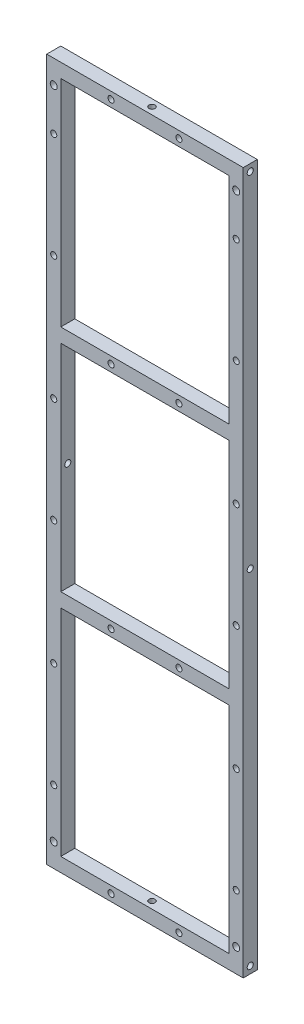
SolidWorks part; units mm, degrees
material "Alumina"
ref_plane "Front Plane" through (0, 0, 0) normal (0, 0, 1) x (1, 0, 0)
ref_plane "Top Plane" through (0, 0, 0) normal (0, 1, 0) x (1, 0, 0)
ref_plane "Right Plane" through (0, 0, 0) normal (1, 0, 0) x (0, 0, -1)
sketch "Sketch1" plane through (0, 0, 0) normal (0, 0, 1) x (1, 0, 0)
  line L0 (36, 144) -> (36, 52)
  line L9 (-42, -150) -> (42, -150)
  line L10 (-42, -150) -> (-42, 150)
  line L11 (-42, 150) -> (42, 150)
  line L12 (42, -150) -> (42, 150)
  line L13 (0, 0) -> (0, 46) construction
  line L15 (-36, -144) -> (36, -144)
  line L16 (-36, -144) -> (-36, -52)
  line L17 (-36, 144) -> (36, 144)
  line L21 (-36, 52) -> (36, 52)
  line L23 (-36, 46) -> (36, 46)
  line L25 (-36, -46) -> (36, -46)
  line L27 (-36, -52) -> (36, -52)
  line L33 (36, 46) -> (36, -46)
  line L34 (-36, 52) -> (-36, 144)
  line L35 (-36, -46) -> (-36, 46)
  line L36 (36, -52) -> (36, -144)
  dimension "D1" = 84
  dimension "D2" = 300
  dimension "D3" = 72
  dimension "D4" = 288
  dimension "D5" = 6
  dimension "D6" = 92
  dimension "D7" = 6
  dimension "D8" = 92
  dimension "D9" = 6
  dimension "D10" = 6
  dimension "D11" = 92
  dimension "D12" = 46
  dimension "D13" = 6
extrude "Boss-Extrude1" add sketch "Sketch1" along normal blind 6
sketch "Sketch2" plane through (42, 0, 0) normal (1, 0, 0) x (0, 0, -1)
  line L0 (-6, 150) -> (0, 150) construction
  line L1 (-6, -150) -> (-6, 150) construction
  line L3 (-3, 147) -> (-3, 0) construction
  circle A0 centre (-3, 147) radius 1.3
  circle A4 centre (-3, 0) radius 1.3
  circle A5 centre (-3, -147) radius 1.3
  circle A6 centre (-3, -294) radius 1.3
  dimension "D1" = 3
  dimension "D3" = 2.6
  dimension "D4" = 3
  dimension "D2" = 4
  dimension "D5" = 147
extrude "Cut-Extrude1" cut sketch "Sketch2" against normal blind 10
mirror "Mirror1" about plane through (0, 0, 0) normal (1, 0, 0) of "Cut-Extrude1"
sketch "Sketch4" plane through (0, 0, 6) normal (0, 0, 1) x (1, 0, 0)
  line L0 (-42, -150) -> (-42, 150) construction
  line L1 (42, -150) -> (42, 150) construction
  line L2 (-42, 150) -> (42, 150) construction
  line L3 (42, 150) -> (-42, 150) construction
  line L4 (-14.5, 147) -> (-14.5, 49) construction
  line L6 (-39, 122) -> (39, 122) construction
  line L7 (-39, 122) -> (-39, 77) construction
  line L8 (-39, 122) -> (-39, 24) construction
  circle A0 centre (-14.5, 147) radius 1.3
  circle A1 centre (14.5, 147) radius 1.3
  circle A8 centre (-39, 122) radius 1.3
  circle A20 centre (-14.5, 49) radius 1.3
  circle A21 centre (14.5, 49) radius 1.3
  circle A22 centre (-14.5, -49) radius 1.3
  circle A23 centre (14.5, -49) radius 1.3
  circle A24 centre (-14.5, -147) radius 1.3
  circle A25 centre (14.5, -147) radius 1.3
  circle A29 centre (39, 122) radius 1.3
  circle A30 centre (39, 77) radius 1.3
  circle A31 centre (-39, 77) radius 1.3
  circle A32 centre (-39, 24) radius 1.3
  circle A33 centre (39, 24) radius 1.3
  circle A34 centre (39, -21) radius 1.3
  circle A35 centre (-39, -21) radius 1.3
  circle A36 centre (-39, -74) radius 1.3
  circle A37 centre (39, -74) radius 1.3
  circle A38 centre (39, -119) radius 1.3
  circle A39 centre (-39, -119) radius 1.3
  dimension "D1" = 27.5
  dimension "D4" = 78
  dimension "D7" = 45
  dimension "D10" = 2.6
  dimension "D11" = 2.6
  dimension "D3" = 3
  dimension "D6" = 3
  dimension "D14" = 2.6
  dimension "D15" = 2
  dimension "D16" = 98
  dimension "D2" = 27.5
  dimension "D5" = 28
  dimension "D9" = 3
  dimension "D13" = 98
  dimension "D12" = 4
  dimension "D8" = 2
extrude "Cut-Extrude3" cut sketch "Sketch4" against normal blind 10
sketch "Sketch5" plane through (0, 150, 0) normal (0, 1, 0) x (1, 0, 0)
  line L0 (42, -6) -> (-42, -6) construction
  circle A0 centre (0, -3) radius 1.3
  point P5 (0, -6)
  dimension "D1" = 3
  dimension "D2" = 2.6
extrude "Cut-Extrude4" cut sketch "Sketch5" against normal blind 10
mirror "Mirror2" about plane through (0, 0, 0) normal (0, 1, 0) of "Cut-Extrude4"
sketch "Sketch6" plane through (0, 0, 6) normal (0, 0, 1) x (1, 0, 0)
  line L0 (-42, 150) -> (-42, -150) construction
  line L1 (42, 150) -> (-42, 150) construction
  circle A0 centre (-39, 140) radius 1.5
  dimension "D1" = 3
  dimension "D2" = 3
  dimension "D3" = 10
extrude "Cut-Extrude5" cut sketch "Sketch6" against normal blind 10
pattern_linear "LPattern1" count 2 spacing 78 along (1, 0, 0) count 2 spacing 280 along (0, -1, 0) of "Cut-Extrude5"
